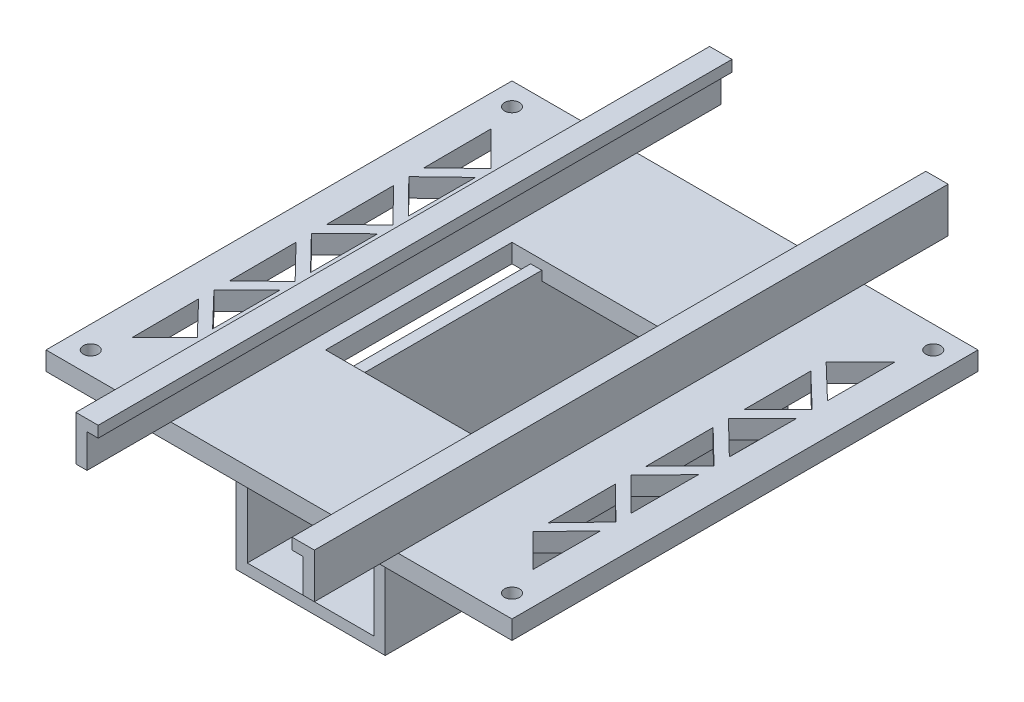
SolidWorks part; units mm, degrees
other "마크업1"
sketch "스케치10" plane through (-62.5, -31.5, -62.5) normal (-0.0294, -0.9842, -0.1746) x (0.6542, 0.1131, -0.7478)
ref_plane "정면" through (0, 0, 0) normal (0, 0, 1) x (1, 0, 0)
ref_plane "윗면" through (0, 0, 0) normal (0, 1, 0) x (1, 0, 0)
ref_plane "우측면" through (0, 0, 0) normal (1, 0, 0) x (0, 0, -1)
ref_axis "기준축1" through (0, 4.2, 0) along (0, -1, 0)
sketch "스케치2" plane through (0, 0, 0) normal (0, 1, 0) x (1, 0, 0)
  line L1 (62.5, 62.5) -> (-62.5, 62.5)
  line L2 (62.5, 62.5) -> (62.5, -62.5)
  line L3 (62.5, -62.5) -> (-62.5, -62.5)
  line L4 (-62.5, 62.5) -> (-62.5, -62.5)
  line L5 (62.5, 62.5) -> (-62.5, -62.5) construction
  line L6 (62.5, -62.5) -> (-62.5, 62.5) construction
  line L7 (-25, 25) -> (25, 25)
  line L8 (-25, 25) -> (-25, -25)
  line L9 (-25, -25) -> (25, -25)
  line L10 (25, 25) -> (25, -25)
  line L11 (-25, 25) -> (25, -25) construction
  line L12 (-25, -25) -> (25, 25) construction
  circle A0 centre (-56.5, 56.5) radius 2
  circle A1 centre (56.5, 56.5) radius 2
  circle A2 centre (-56.5, -56.5) radius 2
  circle A3 centre (56.5, -56.5) radius 2
  point P0 (0, 0)
  point P6 (0, 0)
  dimension "D5" = 4
  dimension "D1" = 125
  dimension "D2" = 125
  dimension "D3" = 50
  dimension "D4" = 50
  dimension "D6" = 6
  dimension "D7" = 6
  dimension "D8" = 6
  dimension "D9" = 6
extrude "보스-돌출1" add sketch "스케치2" along normal mid plane 5
sketch "스케치6" plane through (0, 0, 0) normal (0, 0, 1) x (1, 0, 0)
  line L0 (0, 0) -> (50000, 0) construction
  line L2 (0, 0) -> (0, -50000) construction
  line L3 (-20, 0) -> (-20, -31.5)
  line L4 (-20, -31.5) -> (20, -31.5)
  line L6 (17, -28.5) -> (-17, -28.5)
  line L7 (-17, -28.5) -> (-17, 0)
  line L8 (-17, 0) -> (-20, 0)
  line L9 (17, 0) -> (20, 0)
  line L10 (17, -28.5) -> (17, 0)
  line L11 (20, 0) -> (20, -31.5)
  line L12 (-62.5, -2.5) -> (62.5, -2.5) construction
  point P14 (0, -28.5)
  point P15 (0, -31.5)
  dimension "D1" = 34
  dimension "D2" = 3
  dimension "D3" = 26
  dimension "D4" = 3
extrude "보스-돌출4" add sketch "스케치6" along normal mid plane 108
sketch "스케치11" plane through (0, 0, 0) normal (0, 0, 1) x (1, 0, 0)
  line L0 (-32, 2.5) -> (-32, 14.5)
  line L1 (-62.5, 2.5) -> (62.5, 2.5) construction
  line L2 (-32, 14.5) -> (-26, 14.5)
  line L3 (-26, 14.5) -> (-26, 11.5)
  line L4 (-26, 11.5) -> (-29, 11.5)
  line L5 (-29, 11.5) -> (-29, 2.5)
  line L6 (-32, 2.5) -> (-29, 2.5)
  line L7 (0, -25.3) -> (0, 25.3) construction
  line L8 (32, 2.5) -> (29, 2.5)
  line L9 (29, 11.5) -> (29, 2.5)
  line L10 (26, 11.5) -> (29, 11.5)
  line L11 (26, 14.5) -> (26, 11.5)
  line L12 (32, 14.5) -> (26, 14.5)
  line L13 (32, 2.5) -> (32, 14.5)
  point P8 (-26, 13)
  dimension "D1" = 29
  dimension "D2" = 3
  dimension "D3" = 9
  dimension "D4" = 3
  dimension "D5" = 6
sketch "스케치7" plane through (0, 0, 0) normal (0, 1, 0) x (1, 0, 0)
  line L1 (-40, 40) -> (40, 40)
  line L2 (-40, 40) -> (-40, -40)
  line L3 (-40, -40) -> (40, -40)
  line L4 (40, 40) -> (40, -40)
  line L5 (-40, 40) -> (40, -40) construction
  line L6 (-40, -40) -> (40, 40) construction
  point P0 (0, 0)
  dimension "D1" = 80
  dimension "D2" = 80
extrude "컷-돌출1" [suppressed] cut sketch "스케치7" along normal blind 10
sketch "스케치8" plane through (0, 2.5, 0) normal (0, 1, 0) x (1, 0, 0)
  line L14 (54.1085, 30.5155) -> (54.094, 26.4186) construction
  line L15 (54.0793, 22.2856) -> (54.0155, 4.2857)
  line L20 (44.9633, 35.1872) -> (44.959, 39.3022) construction
  line L41 (53.8296, -48.1728) -> (45.0411, -39.3843)
  line L42 (45.0368, -35.2728) -> (45.018, -17.2728)
  line L43 (44.959, 39.3022) -> (54.1723, 48.5154)
  line L44 (54.1723, 48.5154) -> (54.1085, 30.5155)
  line L83 (62.5, -62.5) -> (-62.5, 62.5) construction
  line L94 (62.5, 62.5) -> (-62.5, -62.5) construction
  line L96 (45.0411, -39.3843) -> (53.8934, -30.1704)
  line L97 (45.0368, -35.2728) -> (53.9081, -26.0392)
  line L98 (53.9081, -26.0392) -> (45.018, -17.2728)
  line L100 (53.9226, -21.9404) -> (45.0138, -13.1555)
  line L101 (45.0138, -13.1555) -> (53.9864, -3.9443)
  line L103 (45.0095, -9.0428) -> (54.001, 0.1878)
  line L104 (54.001, 0.1878) -> (44.9907, 8.9572)
  line L106 (44.9864, 13.0733) -> (54.0155, 4.2857)
  line L107 (44.9864, 13.0733) -> (54.0793, 22.2856)
  line L108 (44.9821, 17.1872) -> (54.094, 26.4186)
  line L110 (54.094, 26.4186) -> (44.9633, 35.1872)
  line L112 (54.1085, 30.5155) -> (44.959, 39.3022)
  line L113 (44.9864, 13.0733) -> (44.9821, 17.1872) construction
  line L114 (44.9821, 17.1872) -> (44.9633, 35.1872)
  line L115 (54.094, 26.4186) -> (54.0793, 22.2856) construction
  line L116 (44.9907, 8.9572) -> (44.9864, 13.0733) construction
  line L117 (54.001, 0.1878) -> (53.9864, -3.9443) construction
  line L118 (53.9864, -3.9443) -> (53.9226, -21.9404)
  line L119 (54.0155, 4.2857) -> (54.001, 0.1878) construction
  line L120 (45.0138, -13.1555) -> (45.0095, -9.0428) construction
  line L121 (45.0095, -9.0428) -> (44.9907, 8.9572)
  line L122 (45.0411, -39.3843) -> (45.0368, -35.2728) construction
  line L123 (53.9081, -26.0392) -> (53.8934, -30.1704) construction
  line L124 (53.8934, -30.1704) -> (53.8296, -48.1728)
  line L125 (53.9226, -21.9404) -> (53.9081, -26.0392) construction
  line L126 (45.018, -17.2728) -> (45.0138, -13.1555) construction
  line L146 (0, -25.3) -> (0, 25.3) construction
  line L155 (-45.018, -17.2728) -> (-45.0138, -13.1555) construction
  line L156 (-53.9226, -21.9404) -> (-53.9081, -26.0392) construction
  line L157 (-53.9081, -26.0392) -> (-53.8934, -30.1704) construction
  line L158 (-45.0411, -39.3843) -> (-45.0368, -35.2728) construction
  line L159 (-45.0138, -13.1555) -> (-45.0095, -9.0428) construction
  line L160 (-54.0155, 4.2857) -> (-54.001, 0.1878) construction
  line L161 (-54.001, 0.1878) -> (-53.9864, -3.9443) construction
  line L162 (-44.9907, 8.9572) -> (-44.9864, 13.0733) construction
  line L163 (-54.094, 26.4186) -> (-54.0793, 22.2856) construction
  line L164 (-44.9864, 13.0733) -> (-44.9821, 17.1872) construction
  line L165 (-44.9633, 35.1872) -> (-44.959, 39.3022) construction
  line L166 (-54.1085, 30.5155) -> (-54.094, 26.4186) construction
  line L178 (-53.8934, -30.1704) -> (-53.8296, -48.1728)
  line L179 (-45.0095, -9.0428) -> (-44.9907, 8.9572)
  line L180 (-53.9864, -3.9443) -> (-53.9226, -21.9404)
  line L181 (-44.9821, 17.1872) -> (-44.9633, 35.1872)
  line L182 (-54.1085, 30.5155) -> (-44.959, 39.3022)
  line L183 (-54.094, 26.4186) -> (-44.9633, 35.1872)
  line L184 (-44.9821, 17.1872) -> (-54.094, 26.4186)
  line L185 (-44.9864, 13.0733) -> (-54.0793, 22.2856)
  line L186 (-44.9864, 13.0733) -> (-54.0155, 4.2857)
  line L187 (-54.001, 0.1878) -> (-44.9907, 8.9572)
  line L188 (-45.0095, -9.0428) -> (-54.001, 0.1878)
  line L189 (-45.0138, -13.1555) -> (-53.9864, -3.9443)
  line L190 (-53.9226, -21.9404) -> (-45.0138, -13.1555)
  line L191 (-53.9081, -26.0392) -> (-45.018, -17.2728)
  line L192 (-45.0368, -35.2728) -> (-53.9081, -26.0392)
  line L193 (-45.0411, -39.3843) -> (-53.8934, -30.1704)
  line L194 (-54.1723, 48.5154) -> (-54.1085, 30.5155)
  line L195 (-44.959, 39.3022) -> (-54.1723, 48.5154)
  line L196 (-45.0368, -35.2728) -> (-45.018, -17.2728)
  line L197 (-53.8296, -48.1728) -> (-45.0411, -39.3843)
  line L202 (-54.0793, 22.2856) -> (-54.0155, 4.2857)
  dimension "D3" = 45
  dimension "D4" = 54
  dimension "D5" = 4
  dimension "D6" = 4
  dimension "D9" = 8.23
  dimension "D10" = 4.115
  dimension "D11" = 18
  dimension "D7" = 18
  dimension "D13" = 8.23
  dimension "D14" = 18
  dimension "D16" = 8.23
  dimension "D17" = 18
  dimension "D19" = 8.23
  dimension "D20" = 8.23
  dimension "D21" = 17.9963
  dimension "D22" = 18
  dimension "D23" = 18.0024
extrude "컷-돌출2" cut sketch "스케치8" against normal blind 5 and the other way through all
pattern_circular "원형 패턴1" [suppressed] count 4 over 360 about axis through (0, 4.2, 0) along (0, -1, 0) of bodies 108
extrude "보스-돌출7" add sketch "스케치11" along normal mid plane 170
sketch "스케치9" [suppressed] plane through (0, 2.5, 0) normal (0, 1, 0) x (1, 0, 0)
  line L0 (-39.3431, -45) -> (-49.8431, -55.5)
  line L1 (-49.8431, -55.5) -> (-24, -55.5)
  line L2 (-24, -55.5) -> (-24, -45)
  line L3 (-24, -45) -> (-39.3431, -45)
  line L4 (62.5, -62.5) -> (-62.5, -62.5) construction
  line L5 (-40, -40) -> (40, -40) construction
  line L6 (62.5, 62.5) -> (-62.5, -62.5) construction
  line L7 (-20, -25) -> (-20, 25) construction
  line L8 (0, -18.7) -> (0, 18.7) construction
  line L9 (24, -45) -> (39.3431, -45)
  line L10 (24, -55.5) -> (24, -45)
  line L11 (49.8431, -55.5) -> (24, -55.5)
  line L12 (39.3431, -45) -> (49.8431, -55.5)
  line L13 (-18.7, 0) -> (18.7, 0) construction
  line L14 (39.3431, 45) -> (49.8431, 55.5)
  line L15 (49.8431, 55.5) -> (24, 55.5)
  line L16 (24, 55.5) -> (24, 45)
  line L17 (24, 45) -> (39.3431, 45)
  line L18 (-24, 45) -> (-39.3431, 45)
  line L19 (-24, 55.5) -> (-24, 45)
  line L20 (-49.8431, 55.5) -> (-24, 55.5)
  line L21 (-39.3431, 45) -> (-49.8431, 55.5)
  dimension "D1" = 7
  dimension "D2" = 5
  dimension "D3" = 4
  dimension "D4" = 4
extrude "컷-돌출3" [suppressed] cut sketch "스케치9" against normal through all
